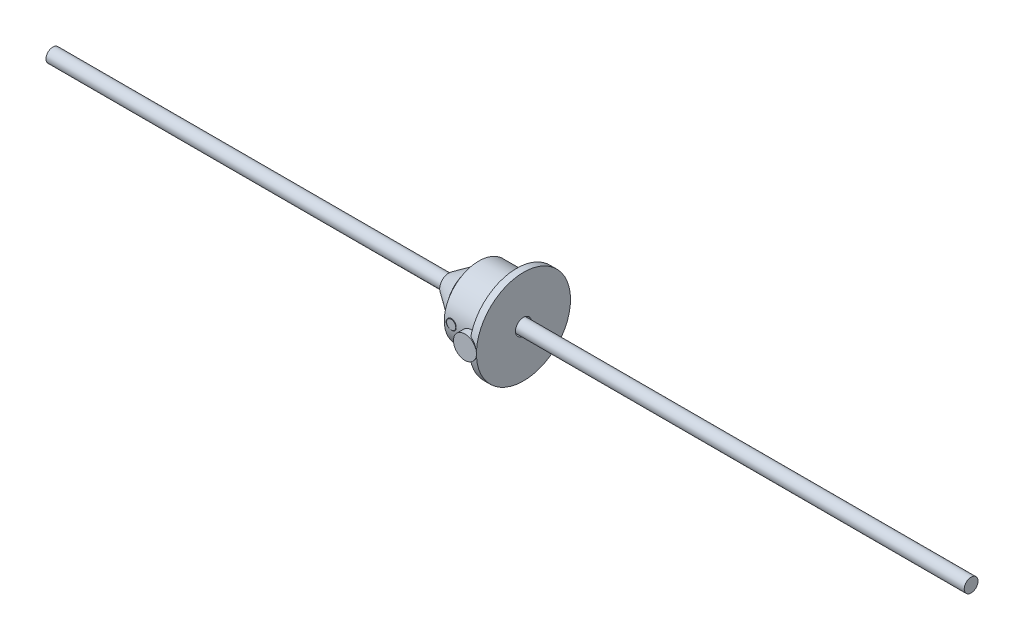
SolidWorks part; units mm, degrees
other "RD S Gear Inner"
other "RD S Gear Outer"
other "RD L Gear Left"
other "RD L Gear Right"
other "RD Ring Gear"
other "RD Pinion"
other "RD S Gear Inner"
ref_plane "Front Plane" through (0, 0, 0) normal (0, 0, 1) x (1, 0, 0)
ref_plane "Top Plane" through (0, 0, 0) normal (0, 1, 0) x (1, 0, 0)
ref_plane "Right Plane" through (0, 0, 0) normal (1, 0, 0) x (0, 0, -1)
sketch "Top View Layout" plane through (0, 0, 0) normal (0, 1, 0) x (1, 0, 0)
  line L0 (-100, 125) -> (100, 125)
  line L1 (0, 125) -> (0, -125)
  line L2 (-100, -125) -> (100, -125)
  line L3 (0, -15) -> (35, -15) construction
  line L4 (35, -15) -> (35, -125) construction
  line L5 (2.5, 114.75) -> (2.5, 135.25) construction
  line L6 (-2.5, 114.75) -> (2.5, 114.75) construction
  line L7 (-8.75, 127) -> (-2.75, 127) construction
  line L8 (-2.5, 114.75) -> (2.5, 114.75) construction
  line L9 (-2.5, 114.75) -> (-2.5, 116.25) construction
  line L10 (-2.5, 116.25) -> (2.5, 116.25) construction
  line L11 (2.5, 114.75) -> (2.5, 116.25) construction
  line L12 (2.5, 135.25) -> (1, 135.25) construction
  line L13 (2.5, 135.25) -> (2.5, 114.75) construction
  line L14 (2.5, 114.75) -> (1, 114.75) construction
  line L15 (1, 135.25) -> (1, 114.75) construction
  line L16 (-4.25, 128.5) -> (-2.75, 128.5) construction
  line L17 (-4.25, 128.5) -> (-4.25, 121.5) construction
  line L18 (-4.25, 121.5) -> (-2.75, 121.5) construction
  line L19 (-2.75, 128.5) -> (-2.75, 121.5) construction
  line L20 (-4.25, 128.5) -> (-2.75, 121.5) construction
  line L21 (-4.25, 121.5) -> (-2.75, 128.5) construction
  line L22 (-8.75, 128.5) -> (-7.25, 128.5) construction
  line L23 (-8.75, 128.5) -> (-8.75, 121.5) construction
  line L24 (-8.75, 121.5) -> (-7.25, 121.5) construction
  line L25 (-7.25, 128.5) -> (-7.25, 121.5) construction
  line L26 (-8.75, 128.5) -> (-7.25, 121.5) construction
  line L27 (-8.75, 121.5) -> (-7.25, 128.5) construction
  line L28 (-8.75, 123) -> (-2.75, 123) construction
  line L29 (-5.75, 123) -> (-5.75, 120.2863) construction
  line L30 (-5.75, 127) -> (-5.75, 129.2691) construction
  point P8 (0, 114.75)
  point P9 (0, 0)
  point P11 (2.5, 125)
  point P16 (2.5, 125)
  point P19 (0, 114.75)
  point P23 (-3.5, 125)
  point P28 (-8, 125)
  dimension "D1" = 250
  dimension "D2" = 200
  dimension "D3" = 35
  dimension "D4" = 15
  dimension "D5" = 5
  dimension "D6" = 20.5
  dimension "D7" = 1.5
  dimension "D8" = 1.5
  dimension "D9" = 1.5
  dimension "D10" = 7
  dimension "D11" = 3.5
  dimension "D12" = 8
  dimension "D13" = 1.5
  dimension "D14" = 1.5
ref_plane "Left" through (100, 0, 0) normal (-1, 0, 0) x (0, 0, 1)
ref_plane "Right" through (-100, 0, 0) normal (-1, 0, 0) x (0, 0, 1)
sketch "Left Wheels" plane through (100, 0, 0) normal (-1, 0, 0) x (0, 0, 1)
  circle A0 centre (125, 0) radius 25
  circle A1 centre (-125, 0) radius 25
  dimension "D1" = 50
  dimension "D2" = 50
sketch "Right Wheels" plane through (-100, 0, 0) normal (-1, 0, 0) x (0, 0, 1)
  circle A0 centre (-125, 0) radius 25 construction
  circle A1 centre (125, 0) radius 25 construction
  circle A2 centre (-125, 0) radius 25
  circle A3 centre (125, 0) radius 25
ref_plane "Rear Differential Pinion Plane" through (0, 0, -114.75) normal (0, 0, 1) x (1, 0, 0)
sketch "Rear Differential Pinion Profile" plane through (0, 0, -114.75) normal (0, 0, 1) x (1, 0, 0)
  circle A0 centre (0, 0) radius 2.5
ref_plane "Rear Differential Ring Gear Plane" through (2.5, 0, 0) normal (1, 0, 0) x (0, 0, -1)
ref_plane "Rear Axle" through (0, 0, -125) normal (0, 0, 1) x (1, 0, 0)
sketch "Rear Differential Ring Gear Profile" plane through (2.5, 0, 0) normal (1, 0, 0) x (0, 0, -1)
  line L0 (114.75, 0) -> (135.25, 0) construction
  circle A0 centre (125, 0) radius 10.25
extrude "Rear Differential Pinion" add sketch "Rear Differential Pinion Profile" against normal blind 1.5 contours A0
extrude "Rear Differential Ring Gear" add sketch "Rear Differential Ring Gear Profile" against normal blind 1.5 separate body contours A0
ref_plane "RD Inner L Gear Plane" through (-2.75, 0, 0) normal (1, 0, 0) x (0, 0, -1)
ref_plane "RD Outer L Gear Plane" through (-8.75, 0, 0) normal (1, 0, 0) x (0, 0, -1)
sketch "RD Inner L Gear Profile" plane through (-2.75, 0, 0) normal (1, 0, 0) x (0, 0, -1)
  circle A0 centre (125, 0) radius 3.5
sketch "RD Outer L Gear Profile" plane through (-8.75, 0, 0) normal (1, 0, 0) x (0, 0, -1)
  line L0 (128.5, 0) -> (121.5, 0) construction
  circle A0 centre (125, 0) radius 3.5
ref_plane "RD Inner S Gear Plane" through (0, 0, -121.5) normal (0, 0, 1) x (1, 0, 0)
ref_plane "RD Outer S Gear Plane" through (0, 0, -128.5) normal (0, 0, 1) x (1, 0, 0)
sketch "RD Inner S Gear Profile" plane through (0, 0, -121.5) normal (0, 0, 1) x (1, 0, 0)
  line L0 (-8.75, 0) -> (-7.25, 0) construction
  circle A0 centre (-5.75, 0) radius 3
sketch "RD Outer S Gear Profile" plane through (0, 0, -128.5) normal (0, 0, 1) x (1, 0, 0)
  line L0 (-8.75, 0) -> (-7.25, 0) construction
  circle A2 centre (-5.75, 0) radius 3
extrude "RD Outer L Gear Extrude" add sketch "RD Outer L Gear Profile" along normal blind 1.5 separate body contours A0
extrude "RD Inner L Gear Extrude" add sketch "RD Inner L Gear Profile" against normal blind 1.5 separate body contours A0
extrude "RD Outer S Gear Extrude" add sketch "RD Outer S Gear Profile" along normal blind 1.5 separate body contours A2
extrude "RD Inner S Gear Extrude" add sketch "RD Inner S Gear Profile" against normal blind 1.5 separate body contours A0
sketch "RD Ring Gear Case Profile" plane through (1, 0, 0) normal (-1, 0, 0) x (0, 0, 1)
  line L0 (-121.5, 3.2113) -> (-121.5, -3.2113)
  line L1 (-128.5, 3.2113) -> (-128.5, -3.2113)
  line L2 (-121.5, 6.6332) -> (-121.5, 3.2113) construction
  line L3 (-128.5, 6.6332) -> (-128.5, 3.2113) construction
  line L4 (-121.5, -3.2113) -> (-121.5, -6.6332) construction
  line L5 (-128.5, -3.2113) -> (-128.5, -6.6332) construction
  circle A0 centre (-125, 0) radius 7.5
  arc A1 (-121.5, 3.2113) -> (-128.5, 3.2113) centre (-125, 0) ccw
  arc A2 (-121.5, -3.2113) -> (-121.5, 3.2113) centre (-125, 0) ccw construction
  arc A3 (-128.5, 3.2113) -> (-128.5, -3.2113) centre (-125, 0) ccw construction
  arc A4 (-128.5, -3.2113) -> (-121.5, -3.2113) centre (-125, 0) ccw
  point P7 (-121.5, 0)
  dimension "D1" = 15
  dimension "D2" = 9.5
extrude "RD Ring Gear Case " add sketch "RD Ring Gear Case Profile" along normal blind 8.25
sketch "Sketch11" plane through (-7.25, 0, 0) normal (-1, 0, 0) x (0, 0, 1)
  circle A0 centre (-125, 0) radius 5.5
  circle A1 centre (-125, 0) radius 4.75
  arc A2 (-121.5, 3.2113) -> (-128.5, 3.2113) centre (-125, 0) ccw construction
  dimension "D1" = 11
extrude "Boss-Extrude8" add sketch "Sketch11" along normal up to vertex up to point (-8.75, 0, -128.5)
fillet "Fillet1" radius 2 1 edges at (-7.25, 0, -119.5)
sketch "Sketch12" plane through (0, 0, -125) normal (0, 0, 1) x (1, 0, 0)
  line L0 (-8.75, 0) -> (-13.75, 0) construction
  line L1 (-8.75, 0) -> (-7.25, 0) construction
  line L2 (-8.75, 0) -> (-7.25, 0) construction
  line L3 (-100, 0) -> (100, 0) construction
  line L4 (-100, 0) -> (100, 0) construction
  line L5 (-8.75, 5.5) -> (-8.75, -5.5) construction
  line L6 (-13.75, 0) -> (-13.75, 2)
  line L7 (-13.75, 2) -> (-8.75, 5.5)
  line L8 (-13.75, 0) -> (-8.75, 0)
  line L9 (-8.75, 0) -> (-8.75, 5.5)
  point P15 (-13.75, 1)
  dimension "D1" = 5
  dimension "D2" = 2
revolve "Revolve1" add sketch "Sketch12" angle 360 about L0
sketch "Sketch13" plane through (2.5, 0, 0) normal (1, 0, 0) x (0, 0, -1)
  circle A0 centre (125, 0) radius 1.75
  dimension "D1" = 3.5
extrude "Cut-Extrude1" cut sketch "Sketch13" against normal through all
sketch "Sketch14" plane through (0, 0, -121.5) normal (0, 0, 1) x (1, 0, 0)
  circle A0 centre (-5.75, 0) radius 1
  dimension "D1" = 2
extrude "Boss-Extrude9" add sketch "Sketch14" along normal blind 4
sketch "Sketch15" plane through (0, 0, -121.5) normal (0, 0, 1) x (1, 0, 0)
  circle A0 centre (-5.75, 0) radius 1.1
  dimension "D1" = 2.2
extrude "Cut-Extrude2" cut sketch "Sketch15" against normal through all both and the other way through all
extrude "Boss-Extrude10" add sketch "Sketch14<2>" against normal blind 4 from surface starting at face at (-2.75, 0, -128.5)
sketch "Sketch14<2>" plane through (0, 0, -121.5) normal (0, 0, 1) x (1, 0, 0) same geometry as "Sketch14"
sketch "Sketch16" plane through (-8.75, 0, 0) normal (-1, 0, 0) x (0, 0, 1)
  circle A0 centre (-125, 0) radius 1.5
  dimension "D1" = 3
extrude "Boss-Extrude11" add sketch "Sketch16" along normal up to vertex (91.25 mm away) up to point (-100, 0, -125)
sketch "Sketch17" plane through (-2.75, 0, 0) normal (1, 0, 0) x (0, 0, -1)
  circle A0 centre (125, 0) radius 1.5 construction
  circle A1 centre (125, 0) radius 1.5
extrude "Boss-Extrude12" add sketch "Sketch17" along normal up to vertex (102.75 mm away) up to point (100, 0, -125)
sketch "Transfer Case Layout" plane through (0, 0, 0) normal (0, 1, 0) x (1, 0, 0)
  line L0 (0, 125) -> (0, -125) construction
  line L1 (-7.5, -13.75) -> (7.5, -13.75)
  line L2 (-7.5, -13.75) -> (-7.5, -16.25)
  line L3 (-7.5, -16.25) -> (7.5, -16.25)
  line L4 (7.5, -13.75) -> (7.5, -16.25)
  line L5 (-7.5, -13.75) -> (7.5, -16.25) construction
  line L6 (-7.5, -16.25) -> (7.5, -13.75) construction
  line L7 (27.5, -13.75) -> (42.5, -13.75)
  line L8 (27.5, -13.75) -> (27.5, -16.25)
  line L9 (27.5, -16.25) -> (42.5, -16.25)
  line L10 (42.5, -13.75) -> (42.5, -16.25)
  line L11 (27.5, -13.75) -> (42.5, -16.25) construction
  line L12 (27.5, -16.25) -> (42.5, -13.75) construction
  line L13 (2.5, -17.25) -> (-2.5, -17.25)
  line L14 (2.5, -17.25) -> (2.5, -16.25)
  line L15 (2.5, -16.25) -> (-2.5, -16.25)
  line L16 (-2.5, -17.25) -> (-2.5, -16.25)
  line L17 (2.5, -17.25) -> (-2.5, -16.25) construction
  line L18 (2.5, -16.25) -> (-2.5, -17.25) construction
  line L19 (-2, -4.75) -> (-2, -10.75)
  line L20 (3.5, -18.25) -> (-3.5, -18.25)
  line L21 (3.5, -18.25) -> (3.5, -16.25)
  line L22 (3.5, -16.25) -> (-3.5, -16.25)
  line L23 (-3.5, -18.25) -> (-3.5, -16.25)
  line L24 (3.5, -18.25) -> (-3.5, -16.25) construction
  line L25 (3.5, -16.25) -> (-3.5, -18.25) construction
  line L26 (2.5, -20) -> (-2.5, -20)
  line L27 (2.5, -20) -> (2.5, -17.5)
  line L28 (2.5, -17.5) -> (-2.5, -17.5)
  line L29 (-2.5, -20) -> (-2.5, -17.5)
  line L30 (2.5, -20) -> (-2.5, -17.5) construction
  line L31 (2.5, -17.5) -> (-2.5, -20) construction
  line L32 (-3.5, -9.25) -> (3.5, -9.25)
  line L33 (-3.5, -9.25) -> (-3.5, -10.75)
  line L34 (-3.5, -10.75) -> (3.5, -10.75)
  line L35 (3.5, -9.25) -> (3.5, -10.75)
  line L36 (-3.5, -9.25) -> (3.5, -10.75) construction
  line L37 (-3.5, -10.75) -> (3.5, -9.25) construction
  line L38 (-3.5, -4.75) -> (3.5, -4.75)
  line L39 (-3.5, -4.75) -> (-3.5, -6.25)
  line L40 (-3.5, -6.25) -> (3.5, -6.25)
  line L41 (3.5, -4.75) -> (3.5, -6.25)
  line L42 (-3.5, -4.75) -> (3.5, -6.25) construction
  line L43 (-3.5, -6.25) -> (3.5, -4.75) construction
  line L44 (2, -4.75) -> (2, -10.75)
  line L45 (0, -6.25) -> (0, -9.25) construction
  line L46 (-5, -2.75) -> (5, -2.75) construction
  line L47 (-5, -2.75) -> (-5, -12.75) construction
  line L48 (-5, -12.75) -> (5, -12.75) construction
  line L49 (5, -2.75) -> (5, -12.75) construction
  line L50 (-5, -2.75) -> (5, -12.75) construction
  line L51 (-5, -12.75) -> (5, -2.75) construction
  line L52 (-6, -22.5) -> (-6, -24)
  line L53 (-2.5, -1.75) -> (2.5, -1.75)
  line L54 (-2.5, -1.75) -> (-2.5, -2.75)
  line L55 (-2.5, -2.75) -> (2.5, -2.75)
  line L56 (2.5, -1.75) -> (2.5, -2.75)
  line L57 (-2.5, -1.75) -> (2.5, -2.75) construction
  line L58 (-2.5, -2.75) -> (2.5, -1.75) construction
  line L59 (-2.5, 1.25) -> (2.5, 1.25)
  line L60 (-2.5, 1.25) -> (-2.5, -0.75)
  line L61 (-2.5, -0.75) -> (2.5, -0.75)
  line L62 (2.5, 1.25) -> (2.5, -0.75)
  line L63 (-2.5, 1.25) -> (2.5, -0.75) construction
  line L64 (-2.5, -0.75) -> (2.5, 1.25) construction
  line L65 (3.5, 0.25) -> (-3.5, 0.25)
  line L66 (3.5, 0.25) -> (3.5, -2.25)
  line L67 (3.5, -2.25) -> (-3.5, -2.25)
  line L68 (-3.5, 0.25) -> (-3.5, -2.25)
  line L69 (3.5, 0.25) -> (-3.5, -2.25) construction
  line L70 (3.5, -2.25) -> (-3.5, 0.25) construction
  line L71 (-2.5, -22.5) -> (2.5, -22.5)
  line L72 (-2.5, -22.5) -> (-2.5, -27.5)
  line L73 (-2.5, -27.5) -> (2.5, -27.5)
  line L74 (2.5, -22.5) -> (2.5, -27.5)
  line L75 (-2.5, -22.5) -> (2.5, -27.5) construction
  line L76 (-2.5, -27.5) -> (2.5, -22.5) construction
  line L77 (-6, -24) -> (6, -24)
  line L78 (6, -24) -> (6, -22.5)
  line L79 (6, -22.5) -> (-6, -22.5)
  line L80 (-4.5, -22.5) -> (-4.5, -24)
  line L81 (4.5, -22.5) -> (4.5, -24)
  line L82 (-6, -24) -> (-6, -33.5) construction
  line L83 (2.5, -29.5) -> (-2.5, -29.5)
  line L84 (2.5, -29.5) -> (2.5, -28)
  line L85 (2.5, -28) -> (-2.5, -28)
  line L86 (-2.5, -29.5) -> (-2.5, -28)
  line L87 (2.5, -29.5) -> (-2.5, -28) construction
  line L88 (2.5, -28) -> (-2.5, -29.5) construction
  line L89 (-4.5, -26.5) -> (4.5, -26.5)
  line L90 (-4.5, -26.5) -> (-4.5, -29.5)
  line L91 (-4.5, -29.5) -> (4.5, -29.5)
  line L92 (4.5, -26.5) -> (4.5, -29.5)
  line L93 (-4.5, -26.5) -> (4.5, -29.5) construction
  line L94 (-4.5, -29.5) -> (4.5, -26.5) construction
  line L95 (6, -24) -> (6, -33.5) construction
  line L96 (-3.5, -33.5) -> (-3.5, -36.5)
  line L97 (6, -36.5) -> (-6, -36.5)
  line L98 (6, -36.5) -> (6, -33.5)
  line L99 (6, -33.5) -> (-6, -33.5)
  line L100 (-6, -36.5) -> (-6, -33.5)
  line L101 (6, -36.5) -> (-6, -33.5) construction
  line L102 (6, -33.5) -> (-6, -36.5) construction
  line L103 (3.5, -33.5) -> (3.5, -36.5)
  line L104 (0, -28) -> (0, -43.1129)
  line L109 (8, -36.5) -> (-8, -36.5)
  line L110 (8, -36.5) -> (8, -33.5)
  line L111 (8, -33.5) -> (-8, -33.5)
  line L112 (-8, -36.5) -> (-8, -33.5)
  line L113 (8, -36.5) -> (-8, -33.5) construction
  line L114 (8, -33.5) -> (-8, -36.5) construction
  line L115 (0, -27.5) -> (0, -9.25)
  line L116 (0, -6.25) -> (0, -1.75)
  line L117 (0, -0.75) -> (0, 11.0375)
  line L118 (35, -22.7597) -> (35, -7.2403)
  point P0 (0, -15)
  point P6 (35, -15)
  point P12 (0, -16.75)
  point P19 (0, -17.25)
  point P24 (0, -18.75)
  point P29 (0, -10)
  point P34 (0, -5.5)
  point P43 (0, -7.75)
  point P50 (0, -2.25)
  point P55 (0, 0.25)
  point P60 (0, -1)
  point P65 (0, -25)
  point P72 (0, -22.5)
  point P79 (0, -28.75)
  point P84 (0, -28)
  point P92 (0, -35)
  point P98 (0, -35)
  point P99 (0, -35)
  point P113 (35, -15)
  dimension "D1" = 2.5
  dimension "D2" = 2.5
  dimension "D3" = 15
  dimension "D4" = 15
  dimension "D5" = 1
  dimension "D6" = 5
  dimension "D7" = 7
  dimension "D8" = 2
  dimension "D9" = 0.25
  dimension "D10" = 2.5
  dimension "D11" = 7
  dimension "D12" = 5
  dimension "D13" = 1.5
  dimension "D14" = 1.5
  dimension "D15" = 1.5
  dimension "D16" = 1.5
  dimension "D17" = 6
  dimension "D18" = 2
  dimension "D19" = 1.5
  dimension "D20" = 5
  dimension "D21" = 1
  dimension "D22" = 2
  dimension "D23" = 1
  dimension "D24" = 7
  dimension "D25" = 2.5
  dimension "D26" = 0.5
  dimension "D27" = 5
  dimension "D28" = 5
  dimension "D29" = 10
  dimension "D30" = 1.5
  dimension "D31" = 12
  dimension "D32" = 1.5
  dimension "D33" = 1.5
  dimension "D34" = 1.5
  dimension "D35" = 0.5
  dimension "D36" = 3
  dimension "D37" = 3
  dimension "D38" = 20
  dimension "D39" = 2.5
  dimension "D40" = 2.5
  dimension "D41" = 7
  dimension "D42" = 2
  dimension "D43" = 16
